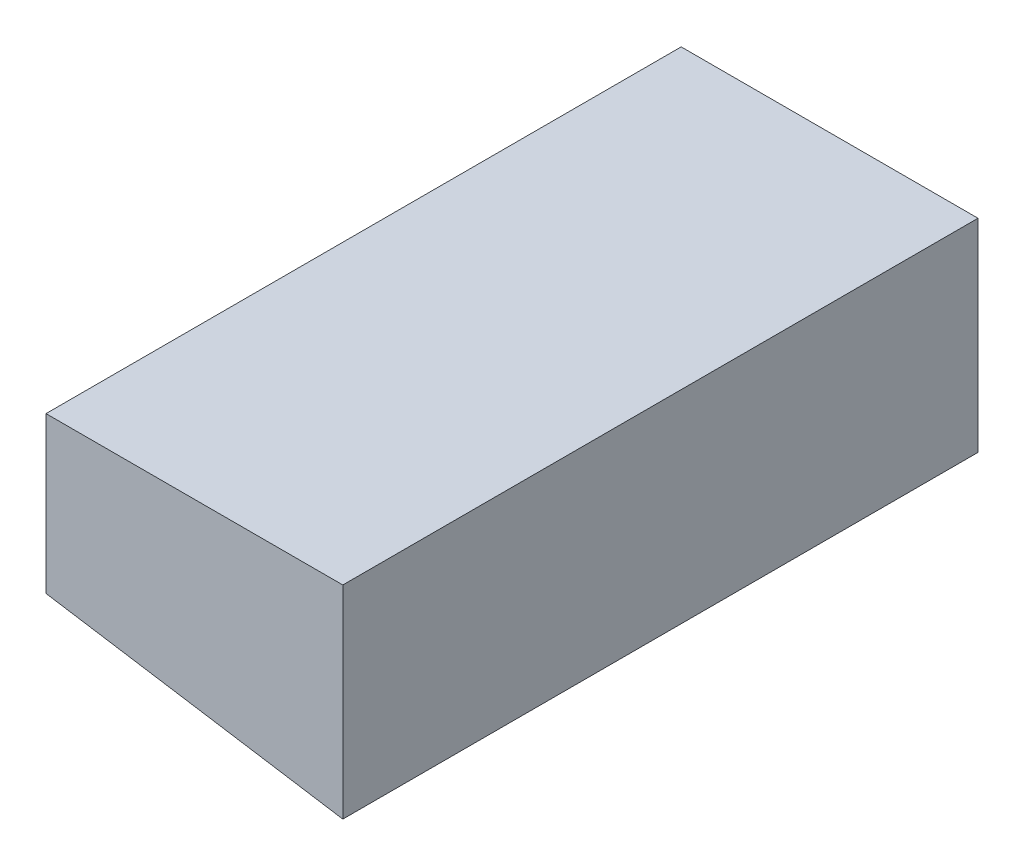
SolidWorks part; units mm, degrees
ref_plane "前视基准面" through (0, 0, 0) normal (0, 0, 1) x (1, 0, 0)
ref_plane "上视基准面" through (0, 0, 0) normal (0, 1, 0) x (1, 0, 0)
ref_plane "右视基准面" through (0, 0, 0) normal (1, 0, 0) x (0, 0, -1)
sketch "草图1" plane through (0, 0, 0) normal (0, 1, 0) x (1, 0, 0)
  line L1 (-46.5351, 23.106) -> (3.4649, 23.106)
  line L2 (-46.5351, 23.106) -> (-46.5351, -83.894)
  line L3 (-46.5351, -83.894) -> (3.4649, -83.894)
  line L4 (3.4649, 23.106) -> (3.4649, -83.894)
  dimension "D1" = 50
  dimension "D2" = 107
extrude "凸台-拉伸1" add sketch "草图1" along normal blind 50
chamfer "倒角1" distance 150 angle 9 1 edges at (-46.5351, 0, 30.394) first distance on face at (-21.5351, 0, 30.394)
